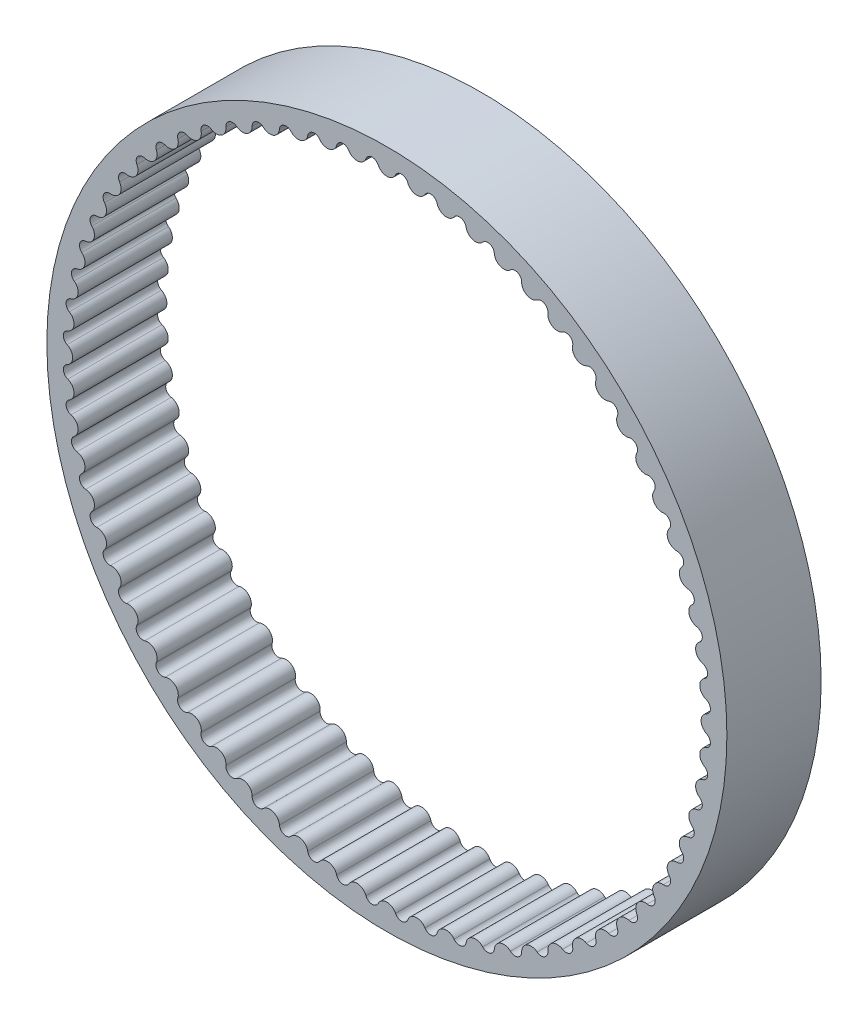
SolidWorks part; units mm, degrees
ref_plane "Front Plane" through (0, 0, 0) normal (0, 0, 1) x (1, 0, 0)
ref_plane "Top Plane" through (0, 0, 0) normal (0, 1, 0) x (1, 0, 0)
ref_plane "Right Plane" through (0, 0, 0) normal (1, 0, 0) x (0, 0, -1)
sketch "Sketch1" plane through (0, 0, 0) normal (0, 0, 1) x (1, 0, 0)
  line L0 (0, 0) -> (0, 20.6151) construction
  line L1 (0, 0) -> (1.9021, 20.5272) construction
  line L2 (0, 0) -> (3.788, 20.2641) construction
  line L3 (-1.9021, 20.5272) -> (0, 0) construction
  circle A0 centre (0, 0) radius 21.6451
  circle A1 centre (0, 0) radius 20.0051
  circle A2 centre (0, 0) radius 20.6151 construction
  circle A10 centre (0, 20.6151) radius 0.61
  circle A101 centre (1.9021, 20.5272) radius 0.61
  circle A102 centre (0.9325, 20.1704) radius 0.4231
  circle A103 centre (-0.9325, 20.1704) radius 0.4231
  circle A104 centre (-1.9021, 20.5272) radius 0.61
  point P16 (-1.8458, 19.9198)
  point P17 (0, 20.0051)
  point P77 (0, 0)
  dimension "OD" = 43.2902
  dimension "Tooth Diameter" = 1.22
  dimension "Belt Thickness" = 1.64
  dimension "Angle" = 5.294
  dimension "D3" = 5.294
sketch "Sketch2" plane through (0, 0, 0) normal (0, 0, 1) x (1, 0, 0)
  circle A0 centre (0, 0) radius 20.0051 construction
  circle A1 centre (0, 0) radius 21.6451 construction
  circle A2 centre (0, 0) radius 20.0051
  circle A3 centre (0, 0) radius 21.6451
extrude "Boss-Extrude1" add sketch "Sketch2" along normal mid plane 6
sketch "Sketch3" plane through (0, 0, 0) normal (0, 0, 1) x (1, 0, 0)
  circle A0 centre (0, 0) radius 20.0051 construction
  circle A1 centre (1.9021, 20.5272) radius 0.61 construction
  circle A2 centre (0.9325, 20.1704) radius 0.4231 construction
  circle A3 centre (0, 20.6151) radius 0.61 construction
  arc A4 (1.8458, 19.9198) -> (0, 20.0051) centre (0, 0) ccw
  arc A5 (1.3296, 20.3165) -> (1.8458, 19.9198) centre (1.9021, 20.5272) ccw
  arc A6 (1.3296, 20.3165) -> (0.5506, 20.3525) centre (0.9325, 20.1704) ccw
  arc A7 (0, 20.0051) -> (0.5506, 20.3525) centre (0, 20.6151) ccw
extrude "Cut-Extrude1" cut sketch "Sketch3" against normal through all both and the other way through all
pattern_circular "CirPattern3" count 68 over 360 about axis through (0, 0, 3) along (0, 0, -1) of "Cut-Extrude1"
ref_axis "Center Axis 1" through (0, 0, 3) along (0, 0, -1)
equation "\"D3@Sketch1\" = \"Angle@Sketch1\""
